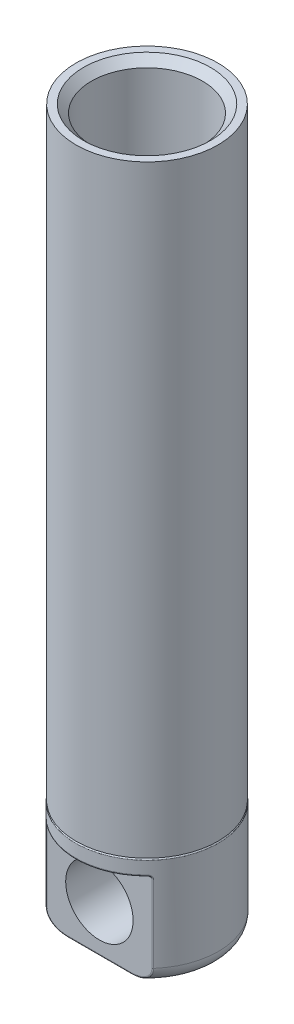
SolidWorks part; units mm, degrees
ref_plane "Front Plane" through (0, 0, 0) normal (0, 0, 1) x (1, 0, 0)
ref_plane "Top Plane" through (0, 0, 0) normal (0, 1, 0) x (1, 0, 0)
ref_plane "Right Plane" through (0, 0, 0) normal (1, 0, 0) x (0, 0, -1)
ref_plane "Plane1" through (0, 0, 0) normal (0, 0, -1) x (-1, 0, 0)
sketch "Sketch1" plane through (0, 0, 0) normal (0, 0, -1) x (-1, 0, 0)
  line L0 (-4.5, -77.6) -> (0, -77.6)
  line L1 (0, -77.6) -> (0, -39.5)
  line L2 (0, -39.5) -> (-4.475, -39.5)
  line L3 (-4.475, -39.5) -> (-4.475, -77.5)
  line L4 (-4.475, -77.5) -> (-4.4, -77.5)
  line L5 (0, -77.6) -> (0, -39.5) construction
  spline S0 degree 3 poles (-4.4, -77.5) (-4.4471, -77.5) (-4.5, -77.5529) (-4.5, -77.6) knots 0 0 0 0 1 1 1 1
revolve "Revolve1" add sketch "Sketch1" angle 360 about L5 reverse direction yes
sketch "Sketch2" plane through (0, -77.6, 0) normal (0, -1, 0) x (1, 0, 0)
  circle A0 centre (0, 0) radius 4.5
extrude "Boss-Extrude1" add sketch "Sketch2" along normal blind 6.9
sketch "Sketch3" plane through (0, -84.5, 0) normal (0, -1, 0) x (1, 0, 0)
  line L0 (3.3541, -3) -> (-3.3541, -3)
  arc A0 (-3.3541, -3) -> (3.3541, -3) centre (0, 0) ccw
extrude "Cut-Extrude1" cut sketch "Sketch3" against normal blind 6
sketch "Sketch4" plane through (0, -84.5, 0) normal (0, -1, 0) x (1, 0, 0)
  line L0 (-3.3541, 3) -> (3.3541, 3)
  arc A0 (3.3541, 3) -> (-3.3541, 3) centre (0, 0) ccw
extrude "Cut-Extrude2" cut sketch "Sketch4" against normal blind 6
hole_wizard "Hole1" positions "Sketch6" profile "Sketch5" legacy
sketch "Sketch6" plane through (0, 0, -3) normal (0, 0, -1) x (-1, 0, 0)
  point P0 (0, -81.5)
sketch "Sketch5" plane through (0, -81.5, -3) normal (1, 0, 0) x (0, 1, 0)
  line L0 (0, 0) -> (0, 7.5)
  line L1 (0, 7.5) -> (2.125, 7.5)
  line L2 (2.125, 7.5) -> (2.125, 0)
  line L3 (2.125, 0) -> (0, 0)
  line L4 (0, 110) -> (0, -10) construction
  dimension "Diameter" = 4.25
  dimension "Depth" = 7.5
hole_wizard "CBORE for M5 Hex Head Bolt1" positions "Sketch8" profile "Sketch7" counterbore size "M5" standard "ANSI Metric"
sketch "Sketch8" plane through (0, -39.5, 0) normal (0, 1, 0) x (1, 0, 0)
  point P0 (0, 0)
sketch "Sketch7" plane through (0, -39.5, 0) normal (1, 0, 0) x (0, 0, 1)
  line L0 (0, 0) -> (0, 37)
  line L1 (0, 37) -> (2.75, 37)
  line L2 (2.75, 37) -> (2.75, 32.866)
  line L3 (2.75, 32.866) -> (3.25, 32)
  line L4 (3.25, 32) -> (3.5, 32)
  line L5 (3.5, 32) -> (3.5, 0.5)
  line L6 (3.5, 0.5) -> (4, 0)
  line L7 (4, 0) -> (0, 0)
  line L8 (-3.5, 0.5) -> (-4, 0) construction
  line L9 (-2.75, 32.866) -> (-3.25, 32) construction
  line L10 (0, 37) -> (-2.75, 37) construction
  line L11 (0, -6.35) -> (0, 107.95) construction
  dimension "Hole Dia." = 5.5
  dimension "Hole Depth" = 37
  dimension "C'Bore Dia." = 7
  dimension "C'Bore Depth" = 32
  dimension "Near C'Sink Dia." = 8
  dimension "Near C'Sink Angle" = 90
  dimension "Mid C'Sink Dia." = 6.5
  dimension "Mid C'Sink Angle" = 60
  dimension "Drill Angle" = 180
fillet "Fillet1" radius 1 3 edges at (0, -76.5, 2.75) (-4.5, -84.5, 0) (4.5, -84.5, 0) tangent propagation no
fillet "Fillet2" radius 0.1 14 edges at (3.3541, -81, 3) (2.9268, -84.2226, 3) (0, -84.5, 3) (0, -78.5, 4.5) (-3.172, -84.0001, 3) (-3.3541, -81, 3) (-2.9268, -84.2226, -3) (-3.3541, -81, -3) (0, -84.5, -3) (0, -78.5, -4.5) (3.172, -84.0001, -3) (3.3541, -81, -3) (0, -78.5, -3) (0, -78.5, 3) tangent propagation no
